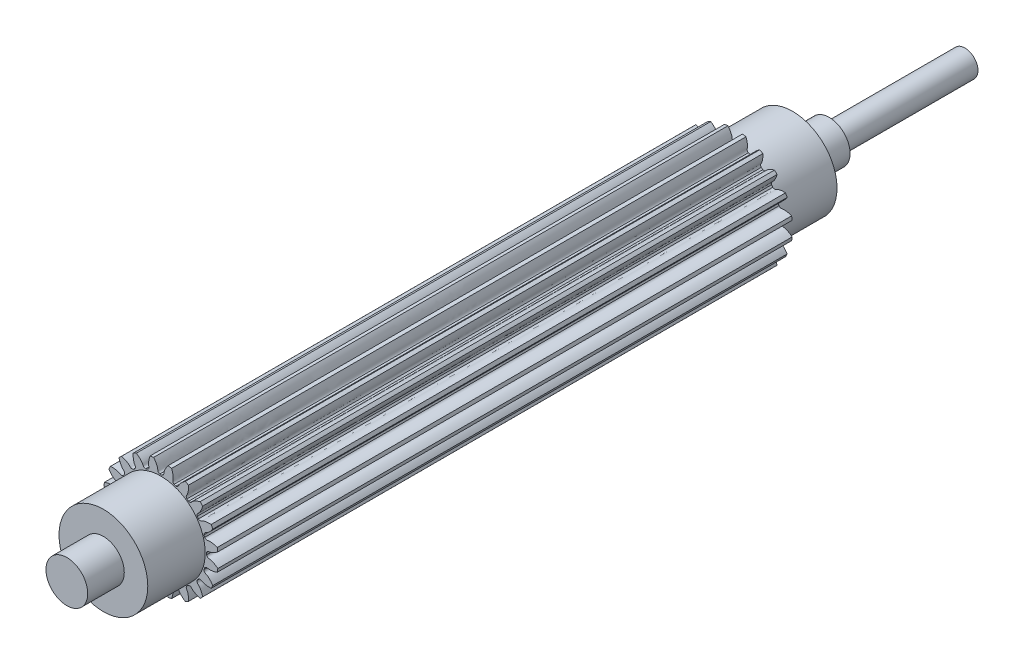
SolidWorks part; units mm, degrees
ref_plane "前视基准面" through (0, 0, 0) normal (0, 0, 1) x (1, 0, 0)
ref_plane "上视基准面" through (0, 0, 0) normal (0, 1, 0) x (1, 0, 0)
ref_plane "右视基准面" through (0, 0, 0) normal (1, 0, 0) x (0, 0, -1)
sketch "草图1" plane through (0, 0, 0) normal (0, 0, 1) x (1, 0, 0)
  circle A0 centre (0, 0) radius 11
extrude "凸台-拉伸1" add sketch "草图1" along normal blind 30
ref_axis "基准轴1" through (0, 0, -1.5) along (0, 0, 1)
sketch "草图2" plane through (0, 0, 0) normal (0, 0, 1) x (1, 0, 0)
  line L0 (0, 0) -> (0, 11) construction
  circle A0 centre (0, 0) radius 11 construction
  arc A1 (0.1933, 8.7479) -> (-0.1933, 8.7479) centre (0, 0) ccw
  arc A2 (3.1812, 12.4983) -> (-3.1812, 12.4983) centre (0, 0) ccw
  spline S0 degree 3 poles (0.1933, 8.7479) (0.6112, 8.8935) (0.5571, 9.1871) (0.6129, 9.47) (0.6189, 9.4976) (0.6263, 9.5286) (0.6353, 9.5632) (0.646, 9.6012) (0.6585, 9.6426) (0.673, 9.6873) (0.6897, 9.7352) (0.7086, 9.7863) (0.7299, 9.8406) (0.7537, 9.8978) (0.7801, 9.958) (0.8094, 10.0211) (0.8415, 10.087) (0.8767, 10.1556) (0.915, 10.2267) (0.9566, 10.3004) (1.0015, 10.3764) (1.05, 10.4548) (1.102, 10.5352) (1.1578, 10.6178) (1.2173, 10.7023) (1.2808, 10.7886) (1.3482, 10.8766) (1.4198, 10.9662) (1.4955, 11.0572) (1.5755, 11.1496) (1.6598, 11.2431) (1.7486, 11.3376) (1.8418, 11.4331) (1.9397, 11.5293) (2.0421, 11.6261) (2.1493, 11.7233) (2.2612, 11.8209) (2.378, 11.9186) (2.4996, 12.0163) (2.6261, 12.1139) (2.7575, 12.2112) (2.9415, 12.3416) (3.0839, 12.4363) (3.1812, 12.4983) knots 0 0 0 0 0.165916 0.170906 0.176664 0.183189 0.190482 0.198542 0.207371 0.216967 0.22733 0.238462 0.250361 0.263027 0.276462 0.290664 0.305634 0.321371 0.337876 0.355149 0.37319 0.391998 0.411574 0.431917 0.453028 0.474907 0.497554 0.520968 0.54515 0.570099 0.595817 0.622302 0.649554 0.677575 0.706363 0.735918 0.766242 0.797333 0.829191 0.861818 0.895212 0.929373 1 1 1 1
  spline S1 degree 3 poles (-0.1933, 8.7479) (-0.6112, 8.8935) (-0.5571, 9.1871) (-0.6129, 9.47) (-0.6189, 9.4976) (-0.6263, 9.5286) (-0.6353, 9.5632) (-0.646, 9.6012) (-0.6585, 9.6426) (-0.673, 9.6873) (-0.6897, 9.7352) (-0.7086, 9.7863) (-0.7299, 9.8406) (-0.7537, 9.8978) (-0.7801, 9.958) (-0.8094, 10.0211) (-0.8415, 10.087) (-0.8767, 10.1556) (-0.915, 10.2267) (-0.9566, 10.3004) (-1.0015, 10.3764) (-1.05, 10.4548) (-1.102, 10.5352) (-1.1578, 10.6178) (-1.2173, 10.7023) (-1.2808, 10.7886) (-1.3482, 10.8766) (-1.4198, 10.9662) (-1.4955, 11.0572) (-1.5755, 11.1496) (-1.6598, 11.2431) (-1.7486, 11.3376) (-1.8418, 11.4331) (-1.9397, 11.5293) (-2.0421, 11.6261) (-2.1493, 11.7233) (-2.2612, 11.8209) (-2.378, 11.9186) (-2.4996, 12.0163) (-2.6261, 12.1139) (-2.7575, 12.2112) (-2.9415, 12.3416) (-3.0839, 12.4363) (-3.1812, 12.4983) knots 0 0 0 0 0.165916 0.170906 0.176664 0.183189 0.190482 0.198542 0.207371 0.216967 0.22733 0.238462 0.250361 0.263027 0.276462 0.290664 0.305634 0.321371 0.337876 0.355149 0.37319 0.391998 0.411574 0.431917 0.453028 0.474907 0.497554 0.520968 0.54515 0.570099 0.595817 0.622302 0.649554 0.677575 0.706363 0.735918 0.766242 0.797333 0.829191 0.861818 0.895212 0.929373 1 1 1 1
extrude "切除-拉伸1" cut sketch "草图2" along normal through all
pattern_circular "阵列(圆周)1" count 20 every 18 about axis through (0, 0, -1.5) along (0, 0, 1) of "切除-拉伸1"
sketch "草图3" plane through (0, 0, 0) normal (0, 0, 1) x (1, 0, 0)
  circle A0 centre (0, 0) radius 10 construction
  dimension "Dn" = 20
sketch "草图4" plane through (0, 0, 30) normal (0, 0, 1) x (1, 0, 0)
  arc A41 (-2.5194, 8.3795) -> (-2.8871, 8.26) centre (0, 0) ccw
  arc A42 (-4.6827, 9.9535) -> (-5.3001, 9.6389) centre (0, 0) ccw
  arc A43 (-4.9855, 7.1908) -> (-5.2983, 6.9635) centre (0, 0) ccw
  arc A44 (-7.5293, 8.0193) -> (-8.0193, 7.5293) centre (0, 0) ccw
  arc A45 (-6.9635, 5.2983) -> (-7.1908, 4.9855) centre (0, 0) ccw
  arc A46 (-9.6389, 5.3001) -> (-9.9535, 4.6827) centre (0, 0) ccw
  arc A47 (-8.26, 2.8871) -> (-8.3795, 2.5194) centre (0, 0) ccw
  arc A48 (-10.805, 2.0622) -> (-10.9134, 1.3777) centre (0, 0) ccw
  arc A49 (-8.7479, 0.1933) -> (-8.7479, -0.1933) centre (0, 0) ccw
  arc A50 (-10.9134, -1.3777) -> (-10.805, -2.0622) centre (0, 0) ccw
  arc A51 (-8.3795, -2.5194) -> (-8.26, -2.8871) centre (0, 0) ccw
  arc A52 (-9.9535, -4.6827) -> (-9.6389, -5.3001) centre (0, 0) ccw
  arc A53 (-7.1908, -4.9855) -> (-6.9635, -5.2983) centre (0, 0) ccw
  arc A54 (-8.0193, -7.5293) -> (-7.5293, -8.0193) centre (0, 0) ccw
  arc A55 (-5.2983, -6.9635) -> (-4.9855, -7.1908) centre (0, 0) ccw
  arc A56 (-5.3001, -9.6389) -> (-4.6827, -9.9535) centre (0, 0) ccw
  arc A57 (-2.8871, -8.26) -> (-2.5194, -8.3795) centre (0, 0) ccw
  arc A58 (-2.0622, -10.805) -> (-1.3777, -10.9134) centre (0, 0) ccw
  arc A59 (-0.1933, -8.7479) -> (0.1933, -8.7479) centre (0, 0) ccw
  arc A60 (1.3777, -10.9134) -> (2.0622, -10.805) centre (0, 0) ccw
  arc A61 (2.5194, -8.3795) -> (2.8871, -8.26) centre (0, 0) ccw
  arc A62 (4.6827, -9.9535) -> (5.3001, -9.6389) centre (0, 0) ccw
  arc A63 (4.9855, -7.1908) -> (5.2983, -6.9635) centre (0, 0) ccw
  arc A64 (7.5293, -8.0193) -> (8.0193, -7.5293) centre (0, 0) ccw
  arc A65 (6.9635, -5.2983) -> (7.1908, -4.9855) centre (0, 0) ccw
  arc A66 (9.6389, -5.3001) -> (9.9535, -4.6827) centre (0, 0) ccw
  arc A67 (8.26, -2.8871) -> (8.3795, -2.5194) centre (0, 0) ccw
  arc A68 (10.805, -2.0622) -> (10.9134, -1.3777) centre (0, 0) ccw
  arc A69 (8.7479, -0.1933) -> (8.7479, 0.1933) centre (0, 0) ccw
  arc A70 (10.9134, 1.3777) -> (10.805, 2.0622) centre (0, 0) ccw
  arc A71 (8.3795, 2.5194) -> (8.26, 2.8871) centre (0, 0) ccw
  arc A72 (9.9535, 4.6827) -> (9.6389, 5.3001) centre (0, 0) ccw
  arc A73 (7.1908, 4.9855) -> (6.9635, 5.2983) centre (0, 0) ccw
  arc A74 (8.0193, 7.5293) -> (7.5293, 8.0193) centre (0, 0) ccw
  arc A75 (5.2983, 6.9635) -> (4.9855, 7.1908) centre (0, 0) ccw
  arc A76 (5.3001, 9.6389) -> (4.6827, 9.9535) centre (0, 0) ccw
  arc A77 (2.8871, 8.26) -> (2.5194, 8.3795) centre (0, 0) ccw
  arc A78 (2.0622, 10.805) -> (1.3777, 10.9134) centre (0, 0) ccw
  arc A79 (0.1933, 8.7479) -> (-0.1933, 8.7479) centre (0, 0) ccw
  arc A80 (-1.3777, 10.9134) -> (-2.0622, 10.805) centre (0, 0) ccw
  arc A81 (-2.5194, 8.3795) -> (-2.8871, 8.26) centre (0, 0) ccw
  arc A82 (-4.6827, 9.9535) -> (-5.3001, 9.6389) centre (0, 0) ccw
  arc A83 (-4.9855, 7.1908) -> (-5.2983, 6.9635) centre (0, 0) ccw
  arc A84 (-7.5293, 8.0193) -> (-8.0193, 7.5293) centre (0, 0) ccw
  arc A85 (-6.9635, 5.2983) -> (-7.1908, 4.9855) centre (0, 0) ccw
  arc A86 (-9.6389, 5.3001) -> (-9.9535, 4.6827) centre (0, 0) ccw
  arc A87 (-8.26, 2.8871) -> (-8.3795, 2.5194) centre (0, 0) ccw
  arc A88 (-10.805, 2.0622) -> (-10.9134, 1.3777) centre (0, 0) ccw
  arc A89 (-8.7479, 0.1933) -> (-8.7479, -0.1933) centre (0, 0) ccw
  arc A90 (-10.9134, -1.3777) -> (-10.805, -2.0622) centre (0, 0) ccw
  arc A91 (-8.3795, -2.5194) -> (-8.26, -2.8871) centre (0, 0) ccw
  arc A92 (-9.9535, -4.6827) -> (-9.6389, -5.3001) centre (0, 0) ccw
  arc A93 (-7.1908, -4.9855) -> (-6.9635, -5.2983) centre (0, 0) ccw
  arc A94 (-8.0193, -7.5293) -> (-7.5293, -8.0193) centre (0, 0) ccw
  arc A95 (-5.2983, -6.9635) -> (-4.9855, -7.1908) centre (0, 0) ccw
  arc A96 (-5.3001, -9.6389) -> (-4.6827, -9.9535) centre (0, 0) ccw
  arc A97 (-2.8871, -8.26) -> (-2.5194, -8.3795) centre (0, 0) ccw
  arc A98 (-2.0622, -10.805) -> (-1.3777, -10.9134) centre (0, 0) ccw
  arc A99 (-0.1933, -8.7479) -> (0.1933, -8.7479) centre (0, 0) ccw
  arc A100 (1.3777, -10.9134) -> (2.0622, -10.805) centre (0, 0) ccw
  arc A101 (2.5194, -8.3795) -> (2.8871, -8.26) centre (0, 0) ccw
  arc A102 (4.6827, -9.9535) -> (5.3001, -9.6389) centre (0, 0) ccw
  arc A103 (4.9855, -7.1908) -> (5.2983, -6.9635) centre (0, 0) ccw
  arc A104 (7.5293, -8.0193) -> (8.0193, -7.5293) centre (0, 0) ccw
  arc A105 (6.9635, -5.2983) -> (7.1908, -4.9855) centre (0, 0) ccw
  arc A106 (9.6389, -5.3001) -> (9.9535, -4.6827) centre (0, 0) ccw
  arc A107 (8.26, -2.8871) -> (8.3795, -2.5194) centre (0, 0) ccw
  arc A108 (10.805, -2.0622) -> (10.9134, -1.3777) centre (0, 0) ccw
  arc A109 (8.7479, -0.1933) -> (8.7479, 0.1933) centre (0, 0) ccw
  arc A110 (10.9134, 1.3777) -> (10.805, 2.0622) centre (0, 0) ccw
  arc A111 (8.3795, 2.5194) -> (8.26, 2.8871) centre (0, 0) ccw
  arc A112 (9.9535, 4.6827) -> (9.6389, 5.3001) centre (0, 0) ccw
  arc A113 (7.1908, 4.9855) -> (6.9635, 5.2983) centre (0, 0) ccw
  arc A114 (8.0193, 7.5293) -> (7.5293, 8.0193) centre (0, 0) ccw
  arc A115 (5.2983, 6.9635) -> (4.9855, 7.1908) centre (0, 0) ccw
  arc A116 (5.3001, 9.6389) -> (4.6827, 9.9535) centre (0, 0) ccw
  arc A117 (2.8871, 8.26) -> (2.5194, 8.3795) centre (0, 0) ccw
  arc A118 (2.0622, 10.805) -> (1.3777, 10.9134) centre (0, 0) ccw
  arc A119 (0.1933, 8.7479) -> (-0.1933, 8.7479) centre (0, 0) ccw
  arc A120 (-1.3777, 10.9134) -> (-2.0622, 10.805) centre (0, 0) ccw
  spline S40 degree 3 poles (3336.3224, 2209.2476) (-31.6692, -18.2216) (-0.9853, 4.2936) (-3.5145, 8.8264) (-3.5419, 8.8721) (-3.5831, 8.935) (-3.6355, 9.0085) (-3.6999, 9.0917) (-3.7774, 9.1837) (-3.8685, 9.2838) (-3.9742, 9.3908) (-4.095, 9.5038) (-4.2316, 9.6217) (-4.3846, 9.7434) (-24.8231, 24.7147) (-146.1058, -103.9868) (3698.5838, 1520.9008) knots -2.504414 -2.504414 -2.504414 -2.504414 0.658484 0.663474 0.675757 0.691111 0.709535 0.73103 0.755596 0.783232 0.813939 0.847717 0.884566 0.924485 0.967475 16.40464 16.40464 16.40464 16.40464 only from (-2.8871, 8.26) to (-4.6827, 9.9535)
  spline S41 degree 3 poles (-3401.5075, -2102.9172) (167.7752, 59.3862) (-5.894, 33.9751) (-5.3021, 9.1747) (-5.2901, 8.9871) (-5.2722, 8.8151) (-5.2496, 8.6588) (-5.2235, 8.5183) (-5.1952, 8.3937) (-5.1658, 8.2848) (-5.1406, 8.204) (-5.1169, 8.136) (-5.0958, 8.0803) (-5.075, 8.0313) (-2.8945, 3.3208) (33.3564, 14.9106) (-3748.3817, -1400.5865) knots -15.062528 -15.062528 -15.062528 -15.062528 0.054403 0.095858 0.134242 0.169555 0.201798 0.23097 0.257071 0.280101 0.300061 0.308889 0.324243 0.336526 0.341516 3.50442 3.50442 3.50442 3.50442 only from (-5.3001, 9.6389) to (-4.9855, 7.1908)
  spline S42 degree 3 poles (2490.3361, 3132.0996) (-24.4884, -27.1161) (-2.2639, 3.779) (-6.07, 7.3084) (-6.1102, 7.3434) (-6.1688, 7.3905) (-6.2413, 7.4441) (-6.3283, 7.5033) (-6.4304, 7.567) (-6.548, 7.634) (-6.6816, 7.7031) (-6.8314, 7.7732) (-6.9977, 7.8432) (-7.1808, 7.9117) (-31.2455, 15.8343) (-106.8212, -144.0465) (3047.578, 2589.3879) knots -2.504414 -2.504414 -2.504414 -2.504414 0.658484 0.663474 0.675757 0.691111 0.709535 0.73103 0.755596 0.783232 0.813939 0.847717 0.884566 0.924485 0.967475 16.40464 16.40464 16.40464 16.40464 only from (-5.2983, 6.9635) to (-7.5293, 8.0193)
  spline S43 degree 3 poles (-2585.1887, -3051.1167) (141.2124, 108.325) (-16.1044, 30.4909) (-7.8777, 7.0872) (-7.8083, 6.9125) (-7.7381, 6.7544) (-7.6683, 6.6128) (-7.6001, 6.4873) (-7.5347, 6.3775) (-7.4731, 6.283) (-7.4241, 6.214) (-7.3806, 6.1566) (-7.3434, 6.1102) (-7.3084, 6.07) (-3.779, 2.2639) (27.1162, 24.4885) (-3132.1178, -2490.3506) knots -15.062528 -15.062528 -15.062528 -15.062528 0.054403 0.095858 0.134242 0.169555 0.201798 0.23097 0.257071 0.280101 0.300061 0.308889 0.324243 0.336526 0.341516 3.50442 3.50442 3.50442 3.50442 only from (-8.0193, 7.5293) to (-6.9635, 5.2983)
  spline S44 degree 3 poles (1400.5784, 3748.36) (-14.9105, -33.3563) (-3.3209, 2.8945) (-8.0313, 5.075) (-8.0803, 5.0958) (-8.1506, 5.1225) (-8.2362, 5.1511) (-8.3373, 5.1805) (-8.454, 5.2095) (-8.5866, 5.2369) (-8.7349, 5.2614) (-8.8991, 5.2818) (-9.0789, 5.2969) (-9.2742, 5.3054) (-34.6093, 5.404) (-57.0802, -170.0059) (2098.2541, 3404.4076) knots -2.504414 -2.504414 -2.504414 -2.504414 0.658484 0.663474 0.675757 0.691111 0.709535 0.73103 0.755596 0.783232 0.813939 0.847717 0.884566 0.924485 0.967475 16.40464 16.40464 16.40464 16.40464 only from (-7.1908, 4.9855) to (-9.6389, 5.3001)
  spline S45 degree 3 poles (-1515.8137, -3700.6517) (100.8267, 146.6603) (-24.7384, 24.022) (-9.6822, 4.306) (-9.5622, 4.1613) (-9.4466, 4.0326) (-9.3365, 3.9195) (-9.2328, 3.8212) (-9.1366, 3.737) (-9.0489, 3.6661) (-8.981, 3.6157) (-8.9219, 3.5745) (-8.8721, 3.5419) (-8.8264, 3.5145) (-4.2936, 0.9853) (18.2217, 31.6693) (-2209.2604, -3336.3418) knots -15.062528 -15.062528 -15.062528 -15.062528 0.054403 0.095858 0.134242 0.169555 0.201798 0.23097 0.257071 0.280101 0.300061 0.308889 0.324243 0.336526 0.341516 3.50442 3.50442 3.50442 3.50442 only from (-9.9535, 4.6827) to (-8.26, 2.8871)
  spline S46 degree 3 poles (173.7222, 3997.7047) (-3.8731, -36.3313) (-4.0528, 1.7266) (-9.2065, 2.3448) (-9.2595, 2.3494) (-9.3346, 2.3531) (-9.4249, 2.3539) (-9.5301, 2.3506) (-9.6501, 2.3421) (-9.7846, 2.3272) (-9.9333, 2.3046) (-10.0957, 2.2733) (-10.2714, 2.2321) (-10.4598, 2.1799) (-34.5853, -5.5554) (-1.7518, -179.324) (943.5384, 3886.1802) knots -2.504414 -2.504414 -2.504414 -2.504414 0.658484 0.663474 0.675757 0.691111 0.709535 0.73103 0.755596 0.783232 0.813939 0.847717 0.884566 0.924485 0.967475 16.40464 16.40464 16.40464 16.40464 only from (-8.3795, 2.5194) to (-10.805, 2.0622)
  spline S47 degree 3 poles (-298.0602, -3987.9411) (50.5714, 170.6393) (-30.9508, 15.2017) (-10.5389, 1.1033) (-10.3801, 1.0027) (-10.2304, 0.9161) (-10.0907, 0.8425) (-9.9617, 0.7811) (-9.8443, 0.7307) (-9.7389, 0.6904) (-9.6588, 0.6634) (-9.5898, 0.6425) (-9.5324, 0.6269) (-9.4805, 0.615) (-4.388, -0.3897) (7.5435, 35.7501) (-1070.1452, -3855.7486) knots -15.062528 -15.062528 -15.062528 -15.062528 0.054403 0.095858 0.134242 0.169555 0.201798 0.23097 0.257071 0.280101 0.300061 0.308889 0.324243 0.336526 0.341516 3.50442 3.50442 3.50442 3.50442 only from (-10.9134, 1.3777) to (-8.7479, 0.1933)
  spline S48 degree 3 poles (-1070.139, 3855.7262) (7.5434, -35.75) (-4.388, 0.3897) (-9.4805, -0.615) (-9.5324, -0.6269) (-9.6049, -0.6466) (-9.691, -0.6738) (-9.79, -0.7094) (-9.9015, -0.7546) (-10.0248, -0.8103) (-10.1593, -0.8777) (-10.3041, -0.9577) (-10.4584, -1.0512) (-10.6215, -1.1591) (-31.1759, -15.9709) (53.7481, -171.0886) (-303.5374, 3987.5464) knots -2.504414 -2.504414 -2.504414 -2.504414 0.658484 0.663474 0.675757 0.691111 0.709535 0.73103 0.755596 0.783232 0.813939 0.847717 0.884566 0.924485 0.967475 16.40464 16.40464 16.40464 16.40464 only from (-8.7479, -0.1933) to (-10.9134, -1.3777)
  spline S49 degree 3 poles (948.8694, -3884.863) (-4.6342, 177.9151) (-34.1335, 4.8934) (-10.364, -2.2074) (-10.1819, -2.254) (-10.0128, -2.2901) (-9.8572, -2.3169) (-9.7155, -2.3355) (-9.5882, -2.3471) (-9.4756, -2.3528) (-9.391, -2.3538) (-9.319, -2.3523) (-9.2595, -2.3494) (-9.2065, -2.3448) (-4.0528, -1.7266) (-3.8731, 36.3314) (173.7233, -3997.7279) knots -15.062528 -15.062528 -15.062528 -15.062528 0.054403 0.095858 0.134242 0.169555 0.201798 0.23097 0.257071 0.280101 0.300061 0.308889 0.324243 0.336526 0.341516 3.50442 3.50442 3.50442 3.50442 only from (-10.805, -2.0622) to (-8.3795, -2.5194)
  spline S50 degree 3 poles (-2209.2476, 3336.3224) (18.2216, -31.6692) (-4.2936, -0.9853) (-8.8264, -3.5145) (-8.8721, -3.5419) (-8.935, -3.5831) (-9.0085, -3.6355) (-9.0917, -3.6999) (-9.1837, -3.7774) (-9.2838, -3.8685) (-9.3908, -3.9742) (-9.5038, -4.095) (-9.6217, -4.2316) (-9.7434, -4.3846) (-24.7147, -24.8231) (103.9868, -146.1058) (-1520.9008, 3698.5838) knots -2.504414 -2.504414 -2.504414 -2.504414 0.658484 0.663474 0.675757 0.691111 0.709535 0.73103 0.755596 0.783232 0.813939 0.847717 0.884566 0.924485 0.967475 16.40464 16.40464 16.40464 16.40464 only from (-8.26, -2.8871) to (-9.9535, -4.6827)
  spline S51 degree 3 poles (2102.9172, -3401.5075) (-59.3862, 167.7752) (-33.9751, -5.894) (-9.1747, -5.3021) (-8.9871, -5.2901) (-8.8151, -5.2722) (-8.6588, -5.2496) (-8.5183, -5.2235) (-8.3937, -5.1952) (-8.2848, -5.1658) (-8.204, -5.1406) (-8.136, -5.1169) (-8.0803, -5.0958) (-8.0313, -5.075) (-3.3208, -2.8945) (-14.9106, 33.3564) (1400.5865, -3748.3817) knots -15.062528 -15.062528 -15.062528 -15.062528 0.054403 0.095858 0.134242 0.169555 0.201798 0.23097 0.257071 0.280101 0.300061 0.308889 0.324243 0.336526 0.341516 3.50442 3.50442 3.50442 3.50442 only from (-9.6389, -5.3001) to (-7.1908, -4.9855)
  spline S52 degree 3 poles (-3132.0996, 2490.3361) (27.1161, -24.4884) (-3.779, -2.2639) (-7.3084, -6.07) (-7.3434, -6.1102) (-7.3905, -6.1688) (-7.4441, -6.2413) (-7.5033, -6.3283) (-7.567, -6.4304) (-7.634, -6.548) (-7.7031, -6.6816) (-7.7732, -6.8314) (-7.8432, -6.9977) (-7.9117, -7.1808) (-15.8343, -31.2455) (144.0465, -106.8212) (-2589.3879, 3047.578) knots -2.504414 -2.504414 -2.504414 -2.504414 0.658484 0.663474 0.675757 0.691111 0.709535 0.73103 0.755596 0.783232 0.813939 0.847717 0.884566 0.924485 0.967475 16.40464 16.40464 16.40464 16.40464 only from (-6.9635, -5.2983) to (-8.0193, -7.5293)
  spline S53 degree 3 poles (3051.1167, -2585.1887) (-108.325, 141.2124) (-30.4909, -16.1044) (-7.0872, -7.8777) (-6.9125, -7.8083) (-6.7544, -7.7381) (-6.6128, -7.6683) (-6.4873, -7.6001) (-6.3775, -7.5347) (-6.283, -7.4731) (-6.214, -7.4241) (-6.1566, -7.3806) (-6.1102, -7.3434) (-6.07, -7.3084) (-2.2639, -3.779) (-24.4885, 27.1162) (2490.3506, -3132.1178) knots -15.062528 -15.062528 -15.062528 -15.062528 0.054403 0.095858 0.134242 0.169555 0.201798 0.23097 0.257071 0.280101 0.300061 0.308889 0.324243 0.336526 0.341516 3.50442 3.50442 3.50442 3.50442 only from (-7.5293, -8.0193) to (-5.2983, -6.9635)
  spline S54 degree 3 poles (-3748.36, 1400.5784) (33.3563, -14.9105) (-2.8945, -3.3209) (-5.075, -8.0313) (-5.0958, -8.0803) (-5.1225, -8.1506) (-5.1511, -8.2362) (-5.1805, -8.3373) (-5.2095, -8.454) (-5.2369, -8.5866) (-5.2614, -8.7349) (-5.2818, -8.8991) (-5.2969, -9.0789) (-5.3054, -9.2742) (-5.404, -34.6093) (170.0059, -57.0802) (-3404.4076, 2098.2541) knots -2.504414 -2.504414 -2.504414 -2.504414 0.658484 0.663474 0.675757 0.691111 0.709535 0.73103 0.755596 0.783232 0.813939 0.847717 0.884566 0.924485 0.967475 16.40464 16.40464 16.40464 16.40464 only from (-4.9855, -7.1908) to (-5.3001, -9.6389)
  spline S55 degree 3 poles (3700.6517, -1515.8137) (-146.6603, 100.8267) (-24.022, -24.7384) (-4.306, -9.6822) (-4.1613, -9.5622) (-4.0326, -9.4466) (-3.9195, -9.3365) (-3.8212, -9.2328) (-3.737, -9.1366) (-3.6661, -9.0489) (-3.6157, -8.981) (-3.5745, -8.9219) (-3.5419, -8.8721) (-3.5145, -8.8264) (-0.9853, -4.2936) (-31.6693, 18.2217) (3336.3418, -2209.2604) knots -15.062528 -15.062528 -15.062528 -15.062528 0.054403 0.095858 0.134242 0.169555 0.201798 0.23097 0.257071 0.280101 0.300061 0.308889 0.324243 0.336526 0.341516 3.50442 3.50442 3.50442 3.50442 only from (-4.6827, -9.9535) to (-2.8871, -8.26)
  spline S56 degree 3 poles (-3997.7047, 173.7222) (36.3313, -3.8731) (-1.7266, -4.0528) (-2.3448, -9.2065) (-2.3494, -9.2595) (-2.3531, -9.3346) (-2.3539, -9.4249) (-2.3506, -9.5301) (-2.3421, -9.6501) (-2.3272, -9.7846) (-2.3046, -9.9333) (-2.2733, -10.0957) (-2.2321, -10.2714) (-2.1799, -10.4598) (5.5554, -34.5853) (179.324, -1.7518) (-3886.1802, 943.5384) knots -2.504414 -2.504414 -2.504414 -2.504414 0.658484 0.663474 0.675757 0.691111 0.709535 0.73103 0.755596 0.783232 0.813939 0.847717 0.884566 0.924485 0.967475 16.40464 16.40464 16.40464 16.40464 only from (-2.5194, -8.3795) to (-2.0622, -10.805)
  spline S57 degree 3 poles (3987.9411, -298.0602) (-170.6393, 50.5714) (-15.2017, -30.9508) (-1.1033, -10.5389) (-1.0027, -10.3801) (-0.9161, -10.2304) (-0.8425, -10.0907) (-0.7811, -9.9617) (-0.7307, -9.8443) (-0.6904, -9.7389) (-0.6634, -9.6588) (-0.6425, -9.5898) (-0.6269, -9.5324) (-0.615, -9.4805) (0.3897, -4.388) (-35.7501, 7.5435) (3855.7486, -1070.1452) knots -15.062528 -15.062528 -15.062528 -15.062528 0.054403 0.095858 0.134242 0.169555 0.201798 0.23097 0.257071 0.280101 0.300061 0.308889 0.324243 0.336526 0.341516 3.50442 3.50442 3.50442 3.50442 only from (-1.3777, -10.9134) to (-0.1933, -8.7479)
  spline S58 degree 3 poles (-3855.7262, -1070.139) (35.75, 7.5434) (-0.3897, -4.388) (0.615, -9.4805) (0.6269, -9.5324) (0.6466, -9.6049) (0.6738, -9.691) (0.7094, -9.79) (0.7546, -9.9015) (0.8103, -10.0248) (0.8777, -10.1593) (0.9577, -10.3041) (1.0512, -10.4584) (1.1591, -10.6215) (15.9709, -31.1759) (171.0886, 53.7481) (-3987.5464, -303.5374) knots -2.504414 -2.504414 -2.504414 -2.504414 0.658484 0.663474 0.675757 0.691111 0.709535 0.73103 0.755596 0.783232 0.813939 0.847717 0.884566 0.924485 0.967475 16.40464 16.40464 16.40464 16.40464 only from (0.1933, -8.7479) to (1.3777, -10.9134)
  spline S59 degree 3 poles (3884.863, 948.8694) (-177.9151, -4.6342) (-4.8934, -34.1335) (2.2074, -10.364) (2.254, -10.1819) (2.2901, -10.0128) (2.3169, -9.8572) (2.3355, -9.7155) (2.3471, -9.5882) (2.3528, -9.4756) (2.3538, -9.391) (2.3523, -9.319) (2.3494, -9.2595) (2.3448, -9.2065) (1.7266, -4.0528) (-36.3314, -3.8731) (3997.7279, 173.7233) knots -15.062528 -15.062528 -15.062528 -15.062528 0.054403 0.095858 0.134242 0.169555 0.201798 0.23097 0.257071 0.280101 0.300061 0.308889 0.324243 0.336526 0.341516 3.50442 3.50442 3.50442 3.50442 only from (2.0622, -10.805) to (2.5194, -8.3795)
  spline S60 degree 3 poles (-3336.3224, -2209.2476) (31.6692, 18.2216) (0.9853, -4.2936) (3.5145, -8.8264) (3.5419, -8.8721) (3.5831, -8.935) (3.6355, -9.0085) (3.6999, -9.0917) (3.7774, -9.1837) (3.8685, -9.2838) (3.9742, -9.3908) (4.095, -9.5038) (4.2316, -9.6217) (4.3846, -9.7434) (24.8231, -24.7147) (146.1058, 103.9868) (-3698.5838, -1520.9008) knots -2.504414 -2.504414 -2.504414 -2.504414 0.658484 0.663474 0.675757 0.691111 0.709535 0.73103 0.755596 0.783232 0.813939 0.847717 0.884566 0.924485 0.967475 16.40464 16.40464 16.40464 16.40464 only from (2.8871, -8.26) to (4.6827, -9.9535)
  spline S61 degree 3 poles (3401.5075, 2102.9172) (-167.7752, -59.3862) (5.894, -33.9751) (5.3021, -9.1747) (5.2901, -8.9871) (5.2722, -8.8151) (5.2496, -8.6588) (5.2235, -8.5183) (5.1952, -8.3937) (5.1658, -8.2848) (5.1406, -8.204) (5.1169, -8.136) (5.0958, -8.0803) (5.075, -8.0313) (2.8945, -3.3208) (-33.3564, -14.9106) (3748.3817, 1400.5865) knots -15.062528 -15.062528 -15.062528 -15.062528 0.054403 0.095858 0.134242 0.169555 0.201798 0.23097 0.257071 0.280101 0.300061 0.308889 0.324243 0.336526 0.341516 3.50442 3.50442 3.50442 3.50442 only from (5.3001, -9.6389) to (4.9855, -7.1908)
  spline S62 degree 3 poles (-2490.3361, -3132.0996) (24.4884, 27.1161) (2.2639, -3.779) (6.07, -7.3084) (6.1102, -7.3434) (6.1688, -7.3905) (6.2413, -7.4441) (6.3283, -7.5033) (6.4304, -7.567) (6.548, -7.634) (6.6816, -7.7031) (6.8314, -7.7732) (6.9977, -7.8432) (7.1808, -7.9117) (31.2455, -15.8343) (106.8212, 144.0465) (-3047.578, -2589.3879) knots -2.504414 -2.504414 -2.504414 -2.504414 0.658484 0.663474 0.675757 0.691111 0.709535 0.73103 0.755596 0.783232 0.813939 0.847717 0.884566 0.924485 0.967475 16.40464 16.40464 16.40464 16.40464 only from (5.2983, -6.9635) to (7.5293, -8.0193)
  spline S63 degree 3 poles (2585.1887, 3051.1167) (-141.2124, -108.325) (16.1044, -30.4909) (7.8777, -7.0872) (7.8083, -6.9125) (7.7381, -6.7544) (7.6683, -6.6128) (7.6001, -6.4873) (7.5347, -6.3775) (7.4731, -6.283) (7.4241, -6.214) (7.3806, -6.1566) (7.3434, -6.1102) (7.3084, -6.07) (3.779, -2.2639) (-27.1162, -24.4885) (3132.1178, 2490.3506) knots -15.062528 -15.062528 -15.062528 -15.062528 0.054403 0.095858 0.134242 0.169555 0.201798 0.23097 0.257071 0.280101 0.300061 0.308889 0.324243 0.336526 0.341516 3.50442 3.50442 3.50442 3.50442 only from (8.0193, -7.5293) to (6.9635, -5.2983)
  spline S64 degree 3 poles (-1400.5784, -3748.36) (14.9105, 33.3563) (3.3209, -2.8945) (8.0313, -5.075) (8.0803, -5.0958) (8.1506, -5.1225) (8.2362, -5.1511) (8.3373, -5.1805) (8.454, -5.2095) (8.5866, -5.2369) (8.7349, -5.2614) (8.8991, -5.2818) (9.0789, -5.2969) (9.2742, -5.3054) (34.6093, -5.404) (57.0802, 170.0059) (-2098.2541, -3404.4076) knots -2.504414 -2.504414 -2.504414 -2.504414 0.658484 0.663474 0.675757 0.691111 0.709535 0.73103 0.755596 0.783232 0.813939 0.847717 0.884566 0.924485 0.967475 16.40464 16.40464 16.40464 16.40464 only from (7.1908, -4.9855) to (9.6389, -5.3001)
  spline S65 degree 3 poles (1515.8137, 3700.6517) (-100.8267, -146.6603) (24.7384, -24.022) (9.6822, -4.306) (9.5622, -4.1613) (9.4466, -4.0326) (9.3365, -3.9195) (9.2328, -3.8212) (9.1366, -3.737) (9.0489, -3.6661) (8.981, -3.6157) (8.9219, -3.5745) (8.8721, -3.5419) (8.8264, -3.5145) (4.2936, -0.9853) (-18.2217, -31.6693) (2209.2604, 3336.3418) knots -15.062528 -15.062528 -15.062528 -15.062528 0.054403 0.095858 0.134242 0.169555 0.201798 0.23097 0.257071 0.280101 0.300061 0.308889 0.324243 0.336526 0.341516 3.50442 3.50442 3.50442 3.50442 only from (9.9535, -4.6827) to (8.26, -2.8871)
  spline S66 degree 3 poles (-173.7222, -3997.7047) (3.8731, 36.3313) (4.0528, -1.7266) (9.2065, -2.3448) (9.2595, -2.3494) (9.3346, -2.3531) (9.4249, -2.3539) (9.5301, -2.3506) (9.6501, -2.3421) (9.7846, -2.3272) (9.9333, -2.3046) (10.0957, -2.2733) (10.2714, -2.2321) (10.4598, -2.1799) (34.5853, 5.5554) (1.7518, 179.324) (-943.5384, -3886.1802) knots -2.504414 -2.504414 -2.504414 -2.504414 0.658484 0.663474 0.675757 0.691111 0.709535 0.73103 0.755596 0.783232 0.813939 0.847717 0.884566 0.924485 0.967475 16.40464 16.40464 16.40464 16.40464 only from (8.3795, -2.5194) to (10.805, -2.0622)
  spline S67 degree 3 poles (298.0602, 3987.9411) (-50.5714, -170.6393) (30.9508, -15.2017) (10.5389, -1.1033) (10.3801, -1.0027) (10.2304, -0.9161) (10.0907, -0.8425) (9.9617, -0.7811) (9.8443, -0.7307) (9.7389, -0.6904) (9.6588, -0.6634) (9.5898, -0.6425) (9.5324, -0.6269) (9.4805, -0.615) (4.388, 0.3897) (-7.5435, -35.7501) (1070.1452, 3855.7486) knots -15.062528 -15.062528 -15.062528 -15.062528 0.054403 0.095858 0.134242 0.169555 0.201798 0.23097 0.257071 0.280101 0.300061 0.308889 0.324243 0.336526 0.341516 3.50442 3.50442 3.50442 3.50442 only from (10.9134, -1.3777) to (8.7479, -0.1933)
  spline S68 degree 3 poles (1070.139, -3855.7262) (-7.5434, 35.75) (4.388, -0.3897) (9.4805, 0.615) (9.5324, 0.6269) (9.6049, 0.6466) (9.691, 0.6738) (9.79, 0.7094) (9.9015, 0.7546) (10.0248, 0.8103) (10.1593, 0.8777) (10.3041, 0.9577) (10.4584, 1.0512) (10.6215, 1.1591) (31.1759, 15.9709) (-53.7481, 171.0886) (303.5374, -3987.5464) knots -2.504414 -2.504414 -2.504414 -2.504414 0.658484 0.663474 0.675757 0.691111 0.709535 0.73103 0.755596 0.783232 0.813939 0.847717 0.884566 0.924485 0.967475 16.40464 16.40464 16.40464 16.40464 only from (8.7479, 0.1933) to (10.9134, 1.3777)
  spline S69 degree 3 poles (-948.8694, 3884.863) (4.6342, -177.9151) (34.1335, -4.8934) (10.364, 2.2074) (10.1819, 2.254) (10.0128, 2.2901) (9.8572, 2.3169) (9.7155, 2.3355) (9.5882, 2.3471) (9.4756, 2.3528) (9.391, 2.3538) (9.319, 2.3523) (9.2595, 2.3494) (9.2065, 2.3448) (4.0528, 1.7266) (3.8731, -36.3314) (-173.7233, 3997.7279) knots -15.062528 -15.062528 -15.062528 -15.062528 0.054403 0.095858 0.134242 0.169555 0.201798 0.23097 0.257071 0.280101 0.300061 0.308889 0.324243 0.336526 0.341516 3.50442 3.50442 3.50442 3.50442 only from (10.805, 2.0622) to (8.3795, 2.5194)
  spline S70 degree 3 poles (2209.2476, -3336.3224) (-18.2216, 31.6692) (4.2936, 0.9853) (8.8264, 3.5145) (8.8721, 3.5419) (8.935, 3.5831) (9.0085, 3.6355) (9.0917, 3.6999) (9.1837, 3.7774) (9.2838, 3.8685) (9.3908, 3.9742) (9.5038, 4.095) (9.6217, 4.2316) (9.7434, 4.3846) (24.7147, 24.8231) (-103.9868, 146.1058) (1520.9008, -3698.5838) knots -2.504414 -2.504414 -2.504414 -2.504414 0.658484 0.663474 0.675757 0.691111 0.709535 0.73103 0.755596 0.783232 0.813939 0.847717 0.884566 0.924485 0.967475 16.40464 16.40464 16.40464 16.40464 only from (8.26, 2.8871) to (9.9535, 4.6827)
  spline S71 degree 3 poles (-2102.9172, 3401.5075) (59.3862, -167.7752) (33.9751, 5.894) (9.1747, 5.3021) (8.9871, 5.2901) (8.8151, 5.2722) (8.6588, 5.2496) (8.5183, 5.2235) (8.3937, 5.1952) (8.2848, 5.1658) (8.204, 5.1406) (8.136, 5.1169) (8.0803, 5.0958) (8.0313, 5.075) (3.3208, 2.8945) (14.9106, -33.3564) (-1400.5865, 3748.3817) knots -15.062528 -15.062528 -15.062528 -15.062528 0.054403 0.095858 0.134242 0.169555 0.201798 0.23097 0.257071 0.280101 0.300061 0.308889 0.324243 0.336526 0.341516 3.50442 3.50442 3.50442 3.50442 only from (9.6389, 5.3001) to (7.1908, 4.9855)
  spline S72 degree 3 poles (3132.0996, -2490.3361) (-27.1161, 24.4884) (3.779, 2.2639) (7.3084, 6.07) (7.3434, 6.1102) (7.3905, 6.1688) (7.4441, 6.2413) (7.5033, 6.3283) (7.567, 6.4304) (7.634, 6.548) (7.7031, 6.6816) (7.7732, 6.8314) (7.8432, 6.9977) (7.9117, 7.1808) (15.8343, 31.2455) (-144.0465, 106.8212) (2589.3879, -3047.578) knots -2.504414 -2.504414 -2.504414 -2.504414 0.658484 0.663474 0.675757 0.691111 0.709535 0.73103 0.755596 0.783232 0.813939 0.847717 0.884566 0.924485 0.967475 16.40464 16.40464 16.40464 16.40464 only from (6.9635, 5.2983) to (8.0193, 7.5293)
  spline S73 degree 3 poles (-3051.1167, 2585.1887) (108.325, -141.2124) (30.4909, 16.1044) (7.0872, 7.8777) (6.9125, 7.8083) (6.7544, 7.7381) (6.6128, 7.6683) (6.4873, 7.6001) (6.3775, 7.5347) (6.283, 7.4731) (6.214, 7.4241) (6.1566, 7.3806) (6.1102, 7.3434) (6.07, 7.3084) (2.2639, 3.779) (24.4885, -27.1162) (-2490.3506, 3132.1178) knots -15.062528 -15.062528 -15.062528 -15.062528 0.054403 0.095858 0.134242 0.169555 0.201798 0.23097 0.257071 0.280101 0.300061 0.308889 0.324243 0.336526 0.341516 3.50442 3.50442 3.50442 3.50442 only from (7.5293, 8.0193) to (5.2983, 6.9635)
  spline S74 degree 3 poles (3748.36, -1400.5784) (-33.3563, 14.9105) (2.8945, 3.3209) (5.075, 8.0313) (5.0958, 8.0803) (5.1225, 8.1506) (5.1511, 8.2362) (5.1805, 8.3373) (5.2095, 8.454) (5.2369, 8.5866) (5.2614, 8.7349) (5.2818, 8.8991) (5.2969, 9.0789) (5.3054, 9.2742) (5.404, 34.6093) (-170.0059, 57.0802) (3404.4076, -2098.2541) knots -2.504414 -2.504414 -2.504414 -2.504414 0.658484 0.663474 0.675757 0.691111 0.709535 0.73103 0.755596 0.783232 0.813939 0.847717 0.884566 0.924485 0.967475 16.40464 16.40464 16.40464 16.40464 only from (4.9855, 7.1908) to (5.3001, 9.6389)
  spline S75 degree 3 poles (-3700.6517, 1515.8137) (146.6603, -100.8267) (24.022, 24.7384) (4.306, 9.6822) (4.1613, 9.5622) (4.0326, 9.4466) (3.9195, 9.3365) (3.8212, 9.2328) (3.737, 9.1366) (3.6661, 9.0489) (3.6157, 8.981) (3.5745, 8.9219) (3.5419, 8.8721) (3.5145, 8.8264) (0.9853, 4.2936) (31.6693, -18.2217) (-3336.3418, 2209.2604) knots -15.062528 -15.062528 -15.062528 -15.062528 0.054403 0.095858 0.134242 0.169555 0.201798 0.23097 0.257071 0.280101 0.300061 0.308889 0.324243 0.336526 0.341516 3.50442 3.50442 3.50442 3.50442 only from (4.6827, 9.9535) to (2.8871, 8.26)
  spline S76 degree 3 poles (3997.7047, -173.7222) (-36.3313, 3.8731) (1.7266, 4.0528) (2.3448, 9.2065) (2.3494, 9.2595) (2.3531, 9.3346) (2.3539, 9.4249) (2.3506, 9.5301) (2.3421, 9.6501) (2.3272, 9.7846) (2.3046, 9.9333) (2.2733, 10.0957) (2.2321, 10.2714) (2.1799, 10.4598) (-5.5554, 34.5853) (-179.324, 1.7518) (3886.1802, -943.5384) knots -2.504414 -2.504414 -2.504414 -2.504414 0.658484 0.663474 0.675757 0.691111 0.709535 0.73103 0.755596 0.783232 0.813939 0.847717 0.884566 0.924485 0.967475 16.40464 16.40464 16.40464 16.40464 only from (2.5194, 8.3795) to (2.0622, 10.805)
  spline S77 degree 3 poles (-3987.9411, 298.0602) (170.6393, -50.5714) (15.2017, 30.9508) (1.1033, 10.5389) (1.0027, 10.3801) (0.9161, 10.2304) (0.8425, 10.0907) (0.7811, 9.9617) (0.7307, 9.8443) (0.6904, 9.7389) (0.6634, 9.6588) (0.6425, 9.5898) (0.6269, 9.5324) (0.615, 9.4805) (-0.3897, 4.388) (35.7501, -7.5435) (-3855.7486, 1070.1452) knots -15.062528 -15.062528 -15.062528 -15.062528 0.054403 0.095858 0.134242 0.169555 0.201798 0.23097 0.257071 0.280101 0.300061 0.308889 0.324243 0.336526 0.341516 3.50442 3.50442 3.50442 3.50442 only from (1.3777, 10.9134) to (0.1933, 8.7479)
  spline S78 degree 3 poles (3855.7262, 1070.139) (-35.75, -7.5434) (0.3897, 4.388) (-0.615, 9.4805) (-0.6269, 9.5324) (-0.6466, 9.6049) (-0.6738, 9.691) (-0.7094, 9.79) (-0.7546, 9.9015) (-0.8103, 10.0248) (-0.8777, 10.1593) (-0.9577, 10.3041) (-1.0512, 10.4584) (-1.1591, 10.6215) (-15.9709, 31.1759) (-171.0886, -53.7481) (3987.5464, 303.5374) knots -2.504414 -2.504414 -2.504414 -2.504414 0.658484 0.663474 0.675757 0.691111 0.709535 0.73103 0.755596 0.783232 0.813939 0.847717 0.884566 0.924485 0.967475 16.40464 16.40464 16.40464 16.40464 only from (-0.1933, 8.7479) to (-1.3777, 10.9134)
  spline S79 degree 3 poles (-3884.863, -948.8694) (177.9151, 4.6342) (4.8934, 34.1335) (-2.2074, 10.364) (-2.254, 10.1819) (-2.2901, 10.0128) (-2.3169, 9.8572) (-2.3355, 9.7155) (-2.3471, 9.5882) (-2.3528, 9.4756) (-2.3538, 9.391) (-2.3523, 9.319) (-2.3494, 9.2595) (-2.3448, 9.2065) (-1.7266, 4.0528) (36.3314, 3.8731) (-3997.7279, -173.7233) knots -15.062528 -15.062528 -15.062528 -15.062528 0.054403 0.095858 0.134242 0.169555 0.201798 0.23097 0.257071 0.280101 0.300061 0.308889 0.324243 0.336526 0.341516 3.50442 3.50442 3.50442 3.50442 only from (-2.0622, 10.805) to (-2.5194, 8.3795)
  spline S80 degree 3 poles (-2.8871, 8.26) (-3.3295, 8.2693) (-3.3688, 8.5653) (-3.5145, 8.8264) (-3.5419, 8.8721) (-3.5831, 8.935) (-3.6355, 9.0085) (-3.6999, 9.0917) (-3.7774, 9.1837) (-3.8685, 9.2838) (-3.9742, 9.3908) (-4.095, 9.5038) (-4.2316, 9.6217) (-4.3846, 9.7434) (-4.5366, 9.8548) (-4.6384, 9.9242) (-4.6827, 9.9535) knots 0.492568 0.492568 0.492568 0.492568 0.658484 0.663474 0.675757 0.691111 0.709535 0.73103 0.755596 0.783232 0.813939 0.847717 0.884566 0.924485 0.967475 1 1 1 1
  spline S81 degree 3 poles (-5.3001, 9.6389) (-5.304, 9.5502) (-5.3073, 9.3937) (-5.3021, 9.1747) (-5.2901, 8.9871) (-5.2722, 8.8151) (-5.2496, 8.6588) (-5.2235, 8.5183) (-5.1952, 8.3937) (-5.1658, 8.2848) (-5.1406, 8.204) (-5.1169, 8.136) (-5.0958, 8.0803) (-5.075, 8.0313) (-4.9494, 7.76) (-4.733, 7.5542) (-4.9855, 7.1908) knots 0 0 0 0 0.054403 0.095858 0.134242 0.169555 0.201798 0.23097 0.257071 0.280101 0.300061 0.308889 0.324243 0.336526 0.341516 0.507432 0.507432 0.507432 0.507432
  spline S82 degree 3 poles (-5.2983, 6.9635) (-5.7219, 6.8357) (-5.8507, 7.1051) (-6.07, 7.3084) (-6.1102, 7.3434) (-6.1688, 7.3905) (-6.2413, 7.4441) (-6.3283, 7.5033) (-6.4304, 7.567) (-6.548, 7.634) (-6.6816, 7.7031) (-6.8314, 7.7732) (-6.9977, 7.8432) (-7.1808, 7.9117) (-7.3598, 7.9706) (-7.4781, 8.0052) (-7.5293, 8.0193) knots 0.492568 0.492568 0.492568 0.492568 0.658484 0.663474 0.675757 0.691111 0.709535 0.73103 0.755596 0.783232 0.813939 0.847717 0.884566 0.924485 0.967475 1 1 1 1
  spline S83 degree 3 poles (-8.0193, 7.5293) (-7.9956, 7.4437) (-7.9503, 7.2939) (-7.8777, 7.0872) (-7.8083, 6.9125) (-7.7381, 6.7544) (-7.6683, 6.6128) (-7.6001, 6.4873) (-7.5347, 6.3775) (-7.4731, 6.283) (-7.4241, 6.214) (-7.3806, 6.1566) (-7.3434, 6.1102) (-7.3084, 6.07) (-7.1051, 5.8507) (-6.8357, 5.7219) (-6.9635, 5.2983) knots 0 0 0 0 0.054403 0.095858 0.134242 0.169555 0.201798 0.23097 0.257071 0.280101 0.300061 0.308889 0.324243 0.336526 0.341516 0.507432 0.507432 0.507432 0.507432
  spline S84 degree 3 poles (-7.1908, 4.9855) (-7.5542, 4.733) (-7.76, 4.9494) (-8.0313, 5.075) (-8.0803, 5.0958) (-8.1506, 5.1225) (-8.2362, 5.1511) (-8.3373, 5.1805) (-8.454, 5.2095) (-8.5866, 5.2369) (-8.7349, 5.2614) (-8.8991, 5.2818) (-9.0789, 5.2969) (-9.2742, 5.3054) (-9.4627, 5.3062) (-9.5859, 5.3025) (-9.6389, 5.3001) knots 0.492568 0.492568 0.492568 0.492568 0.658484 0.663474 0.675757 0.691111 0.709535 0.73103 0.755596 0.783232 0.813939 0.847717 0.884566 0.924485 0.967475 1 1 1 1
  spline S85 degree 3 poles (-9.9535, 4.6827) (-9.9045, 4.6086) (-9.8152, 4.4801) (-9.6822, 4.306) (-9.5622, 4.1613) (-9.4466, 4.0326) (-9.3365, 3.9195) (-9.2328, 3.8212) (-9.1366, 3.737) (-9.0489, 3.6661) (-8.981, 3.6157) (-8.9219, 3.5745) (-8.8721, 3.5419) (-8.8264, 3.5145) (-8.5653, 3.3688) (-8.2693, 3.3295) (-8.26, 2.8871) knots 0 0 0 0 0.054403 0.095858 0.134242 0.169555 0.201798 0.23097 0.257071 0.280101 0.300061 0.308889 0.324243 0.336526 0.341516 0.507432 0.507432 0.507432 0.507432
  spline S86 degree 3 poles (-8.3795, 2.5194) (-8.6471, 2.167) (-8.9096, 2.3092) (-9.2065, 2.3448) (-9.2595, 2.3494) (-9.3346, 2.3531) (-9.4249, 2.3539) (-9.5301, 2.3506) (-9.6501, 2.3421) (-9.7846, 2.3272) (-9.9333, 2.3046) (-10.0957, 2.2733) (-10.2714, 2.2321) (-10.4598, 2.1799) (-10.6392, 2.1223) (-10.7553, 2.0808) (-10.805, 2.0622) knots 0.492568 0.492568 0.492568 0.492568 0.658484 0.663474 0.675757 0.691111 0.709535 0.73103 0.755596 0.783232 0.813939 0.847717 0.884566 0.924485 0.967475 1 1 1 1
  spline S87 degree 3 poles (-10.9134, 1.3777) (-10.8439, 1.3224) (-10.7192, 1.2278) (-10.5389, 1.1033) (-10.3801, 1.0027) (-10.2304, 0.9161) (-10.0907, 0.8425) (-9.9617, 0.7811) (-9.8443, 0.7307) (-9.7389, 0.6904) (-9.6588, 0.6634) (-9.5898, 0.6425) (-9.5324, 0.6269) (-9.4805, 0.615) (-9.1871, 0.5571) (-8.8935, 0.6112) (-8.7479, 0.1933) knots 0 0 0 0 0.054403 0.095858 0.134242 0.169555 0.201798 0.23097 0.257071 0.280101 0.300061 0.308889 0.324243 0.336526 0.341516 0.507432 0.507432 0.507432 0.507432
  spline S88 degree 3 poles (-8.7479, -0.1933) (-8.8935, -0.6112) (-9.1871, -0.5571) (-9.4805, -0.615) (-9.5324, -0.6269) (-9.6049, -0.6466) (-9.691, -0.6738) (-9.79, -0.7094) (-9.9015, -0.7546) (-10.0248, -0.8103) (-10.1593, -0.8777) (-10.3041, -0.9577) (-10.4584, -1.0512) (-10.6215, -1.1591) (-10.7743, -1.2692) (-10.8719, -1.3446) (-10.9134, -1.3777) knots 0.492568 0.492568 0.492568 0.492568 0.658484 0.663474 0.675757 0.691111 0.709535 0.73103 0.755596 0.783232 0.813939 0.847717 0.884566 0.924485 0.967475 1 1 1 1
  spline S89 degree 3 poles (-10.805, -2.0622) (-10.7218, -2.0933) (-10.574, -2.1447) (-10.364, -2.2074) (-10.1819, -2.254) (-10.0128, -2.2901) (-9.8572, -2.3169) (-9.7155, -2.3355) (-9.5882, -2.3471) (-9.4756, -2.3528) (-9.391, -2.3538) (-9.319, -2.3523) (-9.2595, -2.3494) (-9.2065, -2.3448) (-8.9096, -2.3092) (-8.6471, -2.167) (-8.3795, -2.5194) knots 0 0 0 0 0.054403 0.095858 0.134242 0.169555 0.201798 0.23097 0.257071 0.280101 0.300061 0.308889 0.324243 0.336526 0.341516 0.507432 0.507432 0.507432 0.507432
  spline S90 degree 3 poles (-8.26, -2.8871) (-8.2693, -3.3295) (-8.5653, -3.3688) (-8.8264, -3.5145) (-8.8721, -3.5419) (-8.935, -3.5831) (-9.0085, -3.6355) (-9.0917, -3.6999) (-9.1837, -3.7774) (-9.2838, -3.8685) (-9.3908, -3.9742) (-9.5038, -4.095) (-9.6217, -4.2316) (-9.7434, -4.3846) (-9.8548, -4.5366) (-9.9242, -4.6384) (-9.9535, -4.6827) knots 0.492568 0.492568 0.492568 0.492568 0.658484 0.663474 0.675757 0.691111 0.709535 0.73103 0.755596 0.783232 0.813939 0.847717 0.884566 0.924485 0.967475 1 1 1 1
  spline S91 degree 3 poles (-9.6389, -5.3001) (-9.5502, -5.304) (-9.3937, -5.3073) (-9.1747, -5.3021) (-8.9871, -5.2901) (-8.8151, -5.2722) (-8.6588, -5.2496) (-8.5183, -5.2235) (-8.3937, -5.1952) (-8.2848, -5.1658) (-8.204, -5.1406) (-8.136, -5.1169) (-8.0803, -5.0958) (-8.0313, -5.075) (-7.76, -4.9494) (-7.5542, -4.733) (-7.1908, -4.9855) knots 0 0 0 0 0.054403 0.095858 0.134242 0.169555 0.201798 0.23097 0.257071 0.280101 0.300061 0.308889 0.324243 0.336526 0.341516 0.507432 0.507432 0.507432 0.507432
  spline S92 degree 3 poles (-6.9635, -5.2983) (-6.8357, -5.7219) (-7.1051, -5.8507) (-7.3084, -6.07) (-7.3434, -6.1102) (-7.3905, -6.1688) (-7.4441, -6.2413) (-7.5033, -6.3283) (-7.567, -6.4304) (-7.634, -6.548) (-7.7031, -6.6816) (-7.7732, -6.8314) (-7.8432, -6.9977) (-7.9117, -7.1808) (-7.9706, -7.3598) (-8.0052, -7.4781) (-8.0193, -7.5293) knots 0.492568 0.492568 0.492568 0.492568 0.658484 0.663474 0.675757 0.691111 0.709535 0.73103 0.755596 0.783232 0.813939 0.847717 0.884566 0.924485 0.967475 1 1 1 1
  spline S93 degree 3 poles (-7.5293, -8.0193) (-7.4437, -7.9956) (-7.2939, -7.9503) (-7.0872, -7.8777) (-6.9125, -7.8083) (-6.7544, -7.7381) (-6.6128, -7.6683) (-6.4873, -7.6001) (-6.3775, -7.5347) (-6.283, -7.4731) (-6.214, -7.4241) (-6.1566, -7.3806) (-6.1102, -7.3434) (-6.07, -7.3084) (-5.8507, -7.1051) (-5.7219, -6.8357) (-5.2983, -6.9635) knots 0 0 0 0 0.054403 0.095858 0.134242 0.169555 0.201798 0.23097 0.257071 0.280101 0.300061 0.308889 0.324243 0.336526 0.341516 0.507432 0.507432 0.507432 0.507432
  spline S94 degree 3 poles (-4.9855, -7.1908) (-4.733, -7.5542) (-4.9494, -7.76) (-5.075, -8.0313) (-5.0958, -8.0803) (-5.1225, -8.1506) (-5.1511, -8.2362) (-5.1805, -8.3373) (-5.2095, -8.454) (-5.2369, -8.5866) (-5.2614, -8.7349) (-5.2818, -8.8991) (-5.2969, -9.0789) (-5.3054, -9.2742) (-5.3062, -9.4627) (-5.3025, -9.5859) (-5.3001, -9.6389) knots 0.492568 0.492568 0.492568 0.492568 0.658484 0.663474 0.675757 0.691111 0.709535 0.73103 0.755596 0.783232 0.813939 0.847717 0.884566 0.924485 0.967475 1 1 1 1
  spline S95 degree 3 poles (-4.6827, -9.9535) (-4.6086, -9.9045) (-4.4801, -9.8152) (-4.306, -9.6822) (-4.1613, -9.5622) (-4.0326, -9.4466) (-3.9195, -9.3365) (-3.8212, -9.2328) (-3.737, -9.1366) (-3.6661, -9.0489) (-3.6157, -8.981) (-3.5745, -8.9219) (-3.5419, -8.8721) (-3.5145, -8.8264) (-3.3688, -8.5653) (-3.3295, -8.2693) (-2.8871, -8.26) knots 0 0 0 0 0.054403 0.095858 0.134242 0.169555 0.201798 0.23097 0.257071 0.280101 0.300061 0.308889 0.324243 0.336526 0.341516 0.507432 0.507432 0.507432 0.507432
  spline S96 degree 3 poles (-2.5194, -8.3795) (-2.167, -8.6471) (-2.3092, -8.9096) (-2.3448, -9.2065) (-2.3494, -9.2595) (-2.3531, -9.3346) (-2.3539, -9.4249) (-2.3506, -9.5301) (-2.3421, -9.6501) (-2.3272, -9.7846) (-2.3046, -9.9333) (-2.2733, -10.0957) (-2.2321, -10.2714) (-2.1799, -10.4598) (-2.1223, -10.6392) (-2.0808, -10.7553) (-2.0622, -10.805) knots 0.492568 0.492568 0.492568 0.492568 0.658484 0.663474 0.675757 0.691111 0.709535 0.73103 0.755596 0.783232 0.813939 0.847717 0.884566 0.924485 0.967475 1 1 1 1
  spline S97 degree 3 poles (-1.3777, -10.9134) (-1.3224, -10.8439) (-1.2278, -10.7192) (-1.1033, -10.5389) (-1.0027, -10.3801) (-0.9161, -10.2304) (-0.8425, -10.0907) (-0.7811, -9.9617) (-0.7307, -9.8443) (-0.6904, -9.7389) (-0.6634, -9.6588) (-0.6425, -9.5898) (-0.6269, -9.5324) (-0.615, -9.4805) (-0.5571, -9.1871) (-0.6112, -8.8935) (-0.1933, -8.7479) knots 0 0 0 0 0.054403 0.095858 0.134242 0.169555 0.201798 0.23097 0.257071 0.280101 0.300061 0.308889 0.324243 0.336526 0.341516 0.507432 0.507432 0.507432 0.507432
  spline S98 degree 3 poles (0.1933, -8.7479) (0.6112, -8.8935) (0.5571, -9.1871) (0.615, -9.4805) (0.6269, -9.5324) (0.6466, -9.6049) (0.6738, -9.691) (0.7094, -9.79) (0.7546, -9.9015) (0.8103, -10.0248) (0.8777, -10.1593) (0.9577, -10.3041) (1.0512, -10.4584) (1.1591, -10.6215) (1.2692, -10.7743) (1.3446, -10.8719) (1.3777, -10.9134) knots 0.492568 0.492568 0.492568 0.492568 0.658484 0.663474 0.675757 0.691111 0.709535 0.73103 0.755596 0.783232 0.813939 0.847717 0.884566 0.924485 0.967475 1 1 1 1
  spline S99 degree 3 poles (2.0622, -10.805) (2.0933, -10.7218) (2.1447, -10.574) (2.2074, -10.364) (2.254, -10.1819) (2.2901, -10.0128) (2.3169, -9.8572) (2.3355, -9.7155) (2.3471, -9.5882) (2.3528, -9.4756) (2.3538, -9.391) (2.3523, -9.319) (2.3494, -9.2595) (2.3448, -9.2065) (2.3092, -8.9096) (2.167, -8.6471) (2.5194, -8.3795) knots 0 0 0 0 0.054403 0.095858 0.134242 0.169555 0.201798 0.23097 0.257071 0.280101 0.300061 0.308889 0.324243 0.336526 0.341516 0.507432 0.507432 0.507432 0.507432
  spline S100 degree 3 poles (2.8871, -8.26) (3.3295, -8.2693) (3.3688, -8.5653) (3.5145, -8.8264) (3.5419, -8.8721) (3.5831, -8.935) (3.6355, -9.0085) (3.6999, -9.0917) (3.7774, -9.1837) (3.8685, -9.2838) (3.9742, -9.3908) (4.095, -9.5038) (4.2316, -9.6217) (4.3846, -9.7434) (4.5366, -9.8548) (4.6384, -9.9242) (4.6827, -9.9535) knots 0.492568 0.492568 0.492568 0.492568 0.658484 0.663474 0.675757 0.691111 0.709535 0.73103 0.755596 0.783232 0.813939 0.847717 0.884566 0.924485 0.967475 1 1 1 1
  spline S101 degree 3 poles (5.3001, -9.6389) (5.304, -9.5502) (5.3073, -9.3937) (5.3021, -9.1747) (5.2901, -8.9871) (5.2722, -8.8151) (5.2496, -8.6588) (5.2235, -8.5183) (5.1952, -8.3937) (5.1658, -8.2848) (5.1406, -8.204) (5.1169, -8.136) (5.0958, -8.0803) (5.075, -8.0313) (4.9494, -7.76) (4.733, -7.5542) (4.9855, -7.1908) knots 0 0 0 0 0.054403 0.095858 0.134242 0.169555 0.201798 0.23097 0.257071 0.280101 0.300061 0.308889 0.324243 0.336526 0.341516 0.507432 0.507432 0.507432 0.507432
  spline S102 degree 3 poles (5.2983, -6.9635) (5.7219, -6.8357) (5.8507, -7.1051) (6.07, -7.3084) (6.1102, -7.3434) (6.1688, -7.3905) (6.2413, -7.4441) (6.3283, -7.5033) (6.4304, -7.567) (6.548, -7.634) (6.6816, -7.7031) (6.8314, -7.7732) (6.9977, -7.8432) (7.1808, -7.9117) (7.3598, -7.9706) (7.4781, -8.0052) (7.5293, -8.0193) knots 0.492568 0.492568 0.492568 0.492568 0.658484 0.663474 0.675757 0.691111 0.709535 0.73103 0.755596 0.783232 0.813939 0.847717 0.884566 0.924485 0.967475 1 1 1 1
  spline S103 degree 3 poles (8.0193, -7.5293) (7.9956, -7.4437) (7.9503, -7.2939) (7.8777, -7.0872) (7.8083, -6.9125) (7.7381, -6.7544) (7.6683, -6.6128) (7.6001, -6.4873) (7.5347, -6.3775) (7.4731, -6.283) (7.4241, -6.214) (7.3806, -6.1566) (7.3434, -6.1102) (7.3084, -6.07) (7.1051, -5.8507) (6.8357, -5.7219) (6.9635, -5.2983) knots 0 0 0 0 0.054403 0.095858 0.134242 0.169555 0.201798 0.23097 0.257071 0.280101 0.300061 0.308889 0.324243 0.336526 0.341516 0.507432 0.507432 0.507432 0.507432
  spline S104 degree 3 poles (7.1908, -4.9855) (7.5542, -4.733) (7.76, -4.9494) (8.0313, -5.075) (8.0803, -5.0958) (8.1506, -5.1225) (8.2362, -5.1511) (8.3373, -5.1805) (8.454, -5.2095) (8.5866, -5.2369) (8.7349, -5.2614) (8.8991, -5.2818) (9.0789, -5.2969) (9.2742, -5.3054) (9.4627, -5.3062) (9.5859, -5.3025) (9.6389, -5.3001) knots 0.492568 0.492568 0.492568 0.492568 0.658484 0.663474 0.675757 0.691111 0.709535 0.73103 0.755596 0.783232 0.813939 0.847717 0.884566 0.924485 0.967475 1 1 1 1
  spline S105 degree 3 poles (9.9535, -4.6827) (9.9045, -4.6086) (9.8152, -4.4801) (9.6822, -4.306) (9.5622, -4.1613) (9.4466, -4.0326) (9.3365, -3.9195) (9.2328, -3.8212) (9.1366, -3.737) (9.0489, -3.6661) (8.981, -3.6157) (8.9219, -3.5745) (8.8721, -3.5419) (8.8264, -3.5145) (8.5653, -3.3688) (8.2693, -3.3295) (8.26, -2.8871) knots 0 0 0 0 0.054403 0.095858 0.134242 0.169555 0.201798 0.23097 0.257071 0.280101 0.300061 0.308889 0.324243 0.336526 0.341516 0.507432 0.507432 0.507432 0.507432
  spline S106 degree 3 poles (8.3795, -2.5194) (8.6471, -2.167) (8.9096, -2.3092) (9.2065, -2.3448) (9.2595, -2.3494) (9.3346, -2.3531) (9.4249, -2.3539) (9.5301, -2.3506) (9.6501, -2.3421) (9.7846, -2.3272) (9.9333, -2.3046) (10.0957, -2.2733) (10.2714, -2.2321) (10.4598, -2.1799) (10.6392, -2.1223) (10.7553, -2.0808) (10.805, -2.0622) knots 0.492568 0.492568 0.492568 0.492568 0.658484 0.663474 0.675757 0.691111 0.709535 0.73103 0.755596 0.783232 0.813939 0.847717 0.884566 0.924485 0.967475 1 1 1 1
  spline S107 degree 3 poles (10.9134, -1.3777) (10.8439, -1.3224) (10.7192, -1.2278) (10.5389, -1.1033) (10.3801, -1.0027) (10.2304, -0.9161) (10.0907, -0.8425) (9.9617, -0.7811) (9.8443, -0.7307) (9.7389, -0.6904) (9.6588, -0.6634) (9.5898, -0.6425) (9.5324, -0.6269) (9.4805, -0.615) (9.1871, -0.5571) (8.8935, -0.6112) (8.7479, -0.1933) knots 0 0 0 0 0.054403 0.095858 0.134242 0.169555 0.201798 0.23097 0.257071 0.280101 0.300061 0.308889 0.324243 0.336526 0.341516 0.507432 0.507432 0.507432 0.507432
  spline S108 degree 3 poles (8.7479, 0.1933) (8.8935, 0.6112) (9.1871, 0.5571) (9.4805, 0.615) (9.5324, 0.6269) (9.6049, 0.6466) (9.691, 0.6738) (9.79, 0.7094) (9.9015, 0.7546) (10.0248, 0.8103) (10.1593, 0.8777) (10.3041, 0.9577) (10.4584, 1.0512) (10.6215, 1.1591) (10.7743, 1.2692) (10.8719, 1.3446) (10.9134, 1.3777) knots 0.492568 0.492568 0.492568 0.492568 0.658484 0.663474 0.675757 0.691111 0.709535 0.73103 0.755596 0.783232 0.813939 0.847717 0.884566 0.924485 0.967475 1 1 1 1
  spline S109 degree 3 poles (10.805, 2.0622) (10.7218, 2.0933) (10.574, 2.1447) (10.364, 2.2074) (10.1819, 2.254) (10.0128, 2.2901) (9.8572, 2.3169) (9.7155, 2.3355) (9.5882, 2.3471) (9.4756, 2.3528) (9.391, 2.3538) (9.319, 2.3523) (9.2595, 2.3494) (9.2065, 2.3448) (8.9096, 2.3092) (8.6471, 2.167) (8.3795, 2.5194) knots 0 0 0 0 0.054403 0.095858 0.134242 0.169555 0.201798 0.23097 0.257071 0.280101 0.300061 0.308889 0.324243 0.336526 0.341516 0.507432 0.507432 0.507432 0.507432
  spline S110 degree 3 poles (8.26, 2.8871) (8.2693, 3.3295) (8.5653, 3.3688) (8.8264, 3.5145) (8.8721, 3.5419) (8.935, 3.5831) (9.0085, 3.6355) (9.0917, 3.6999) (9.1837, 3.7774) (9.2838, 3.8685) (9.3908, 3.9742) (9.5038, 4.095) (9.6217, 4.2316) (9.7434, 4.3846) (9.8548, 4.5366) (9.9242, 4.6384) (9.9535, 4.6827) knots 0.492568 0.492568 0.492568 0.492568 0.658484 0.663474 0.675757 0.691111 0.709535 0.73103 0.755596 0.783232 0.813939 0.847717 0.884566 0.924485 0.967475 1 1 1 1
  spline S111 degree 3 poles (9.6389, 5.3001) (9.5502, 5.304) (9.3937, 5.3073) (9.1747, 5.3021) (8.9871, 5.2901) (8.8151, 5.2722) (8.6588, 5.2496) (8.5183, 5.2235) (8.3937, 5.1952) (8.2848, 5.1658) (8.204, 5.1406) (8.136, 5.1169) (8.0803, 5.0958) (8.0313, 5.075) (7.76, 4.9494) (7.5542, 4.733) (7.1908, 4.9855) knots 0 0 0 0 0.054403 0.095858 0.134242 0.169555 0.201798 0.23097 0.257071 0.280101 0.300061 0.308889 0.324243 0.336526 0.341516 0.507432 0.507432 0.507432 0.507432
  spline S112 degree 3 poles (6.9635, 5.2983) (6.8357, 5.7219) (7.1051, 5.8507) (7.3084, 6.07) (7.3434, 6.1102) (7.3905, 6.1688) (7.4441, 6.2413) (7.5033, 6.3283) (7.567, 6.4304) (7.634, 6.548) (7.7031, 6.6816) (7.7732, 6.8314) (7.8432, 6.9977) (7.9117, 7.1808) (7.9706, 7.3598) (8.0052, 7.4781) (8.0193, 7.5293) knots 0.492568 0.492568 0.492568 0.492568 0.658484 0.663474 0.675757 0.691111 0.709535 0.73103 0.755596 0.783232 0.813939 0.847717 0.884566 0.924485 0.967475 1 1 1 1
  spline S113 degree 3 poles (7.5293, 8.0193) (7.4437, 7.9956) (7.2939, 7.9503) (7.0872, 7.8777) (6.9125, 7.8083) (6.7544, 7.7381) (6.6128, 7.6683) (6.4873, 7.6001) (6.3775, 7.5347) (6.283, 7.4731) (6.214, 7.4241) (6.1566, 7.3806) (6.1102, 7.3434) (6.07, 7.3084) (5.8507, 7.1051) (5.7219, 6.8357) (5.2983, 6.9635) knots 0 0 0 0 0.054403 0.095858 0.134242 0.169555 0.201798 0.23097 0.257071 0.280101 0.300061 0.308889 0.324243 0.336526 0.341516 0.507432 0.507432 0.507432 0.507432
  spline S114 degree 3 poles (4.9855, 7.1908) (4.733, 7.5542) (4.9494, 7.76) (5.075, 8.0313) (5.0958, 8.0803) (5.1225, 8.1506) (5.1511, 8.2362) (5.1805, 8.3373) (5.2095, 8.454) (5.2369, 8.5866) (5.2614, 8.7349) (5.2818, 8.8991) (5.2969, 9.0789) (5.3054, 9.2742) (5.3062, 9.4627) (5.3025, 9.5859) (5.3001, 9.6389) knots 0.492568 0.492568 0.492568 0.492568 0.658484 0.663474 0.675757 0.691111 0.709535 0.73103 0.755596 0.783232 0.813939 0.847717 0.884566 0.924485 0.967475 1 1 1 1
  spline S115 degree 3 poles (4.6827, 9.9535) (4.6086, 9.9045) (4.4801, 9.8152) (4.306, 9.6822) (4.1613, 9.5622) (4.0326, 9.4466) (3.9195, 9.3365) (3.8212, 9.2328) (3.737, 9.1366) (3.6661, 9.0489) (3.6157, 8.981) (3.5745, 8.9219) (3.5419, 8.8721) (3.5145, 8.8264) (3.3688, 8.5653) (3.3295, 8.2693) (2.8871, 8.26) knots 0 0 0 0 0.054403 0.095858 0.134242 0.169555 0.201798 0.23097 0.257071 0.280101 0.300061 0.308889 0.324243 0.336526 0.341516 0.507432 0.507432 0.507432 0.507432
  spline S116 degree 3 poles (2.5194, 8.3795) (2.167, 8.6471) (2.3092, 8.9096) (2.3448, 9.2065) (2.3494, 9.2595) (2.3531, 9.3346) (2.3539, 9.4249) (2.3506, 9.5301) (2.3421, 9.6501) (2.3272, 9.7846) (2.3046, 9.9333) (2.2733, 10.0957) (2.2321, 10.2714) (2.1799, 10.4598) (2.1223, 10.6392) (2.0808, 10.7553) (2.0622, 10.805) knots 0.492568 0.492568 0.492568 0.492568 0.658484 0.663474 0.675757 0.691111 0.709535 0.73103 0.755596 0.783232 0.813939 0.847717 0.884566 0.924485 0.967475 1 1 1 1
  spline S117 degree 3 poles (1.3777, 10.9134) (1.3224, 10.8439) (1.2278, 10.7192) (1.1033, 10.5389) (1.0027, 10.3801) (0.9161, 10.2304) (0.8425, 10.0907) (0.7811, 9.9617) (0.7307, 9.8443) (0.6904, 9.7389) (0.6634, 9.6588) (0.6425, 9.5898) (0.6269, 9.5324) (0.615, 9.4805) (0.5571, 9.1871) (0.6112, 8.8935) (0.1933, 8.7479) knots 0 0 0 0 0.054403 0.095858 0.134242 0.169555 0.201798 0.23097 0.257071 0.280101 0.300061 0.308889 0.324243 0.336526 0.341516 0.507432 0.507432 0.507432 0.507432
  spline S118 degree 3 poles (-0.1933, 8.7479) (-0.6112, 8.8935) (-0.5571, 9.1871) (-0.615, 9.4805) (-0.6269, 9.5324) (-0.6466, 9.6049) (-0.6738, 9.691) (-0.7094, 9.79) (-0.7546, 9.9015) (-0.8103, 10.0248) (-0.8777, 10.1593) (-0.9577, 10.3041) (-1.0512, 10.4584) (-1.1591, 10.6215) (-1.2692, 10.7743) (-1.3446, 10.8719) (-1.3777, 10.9134) knots 0.492568 0.492568 0.492568 0.492568 0.658484 0.663474 0.675757 0.691111 0.709535 0.73103 0.755596 0.783232 0.813939 0.847717 0.884566 0.924485 0.967475 1 1 1 1
  spline S119 degree 3 poles (-2.0622, 10.805) (-2.0933, 10.7218) (-2.1447, 10.574) (-2.2074, 10.364) (-2.254, 10.1819) (-2.2901, 10.0128) (-2.3169, 9.8572) (-2.3355, 9.7155) (-2.3471, 9.5882) (-2.3528, 9.4756) (-2.3538, 9.391) (-2.3523, 9.319) (-2.3494, 9.2595) (-2.3448, 9.2065) (-2.3092, 8.9096) (-2.167, 8.6471) (-2.5194, 8.3795) knots 0 0 0 0 0.054403 0.095858 0.134242 0.169555 0.201798 0.23097 0.257071 0.280101 0.300061 0.308889 0.324243 0.336526 0.341516 0.507432 0.507432 0.507432 0.507432
  dimension "D1" = 0
extrude "凸台-拉伸2" add sketch "草图4" along normal blind 80
sketch "草图5" plane through (0, 0, 0) normal (0, 0, -1) x (-1, 0, 0)
  circle A0 centre (0, 0) radius 8.5
  dimension "D1" = 17
extrude "凸台-拉伸3" add sketch "草图5" along normal blind 11
sketch "草图6" plane through (0, 0, -11) normal (0, 0, -1) x (-1, 0, 0)
  circle A0 centre (0, 0) radius 4
  dimension "D1" = 8
extrude "凸台-拉伸4" add sketch "草图6" along normal blind 7
sketch "草图7" plane through (0, 0, -18) normal (0, 0, -1) x (-1, 0, 0)
  circle A0 centre (0, 0) radius 1.5
  dimension "D1" = 3
sketch "草图8" plane through (0, 0, 110) normal (0, 0, 1) x (1, 0, 0)
  circle A0 centre (0, 0) radius 8.5
  dimension "D1" = 17
extrude "凸台-拉伸5" add sketch "草图8" along normal blind 11
sketch "草图9" plane through (0, 0, 121) normal (0, 0, 1) x (1, 0, 0)
  circle A0 centre (0, 0) radius 4
  dimension "D1" = 8
extrude "凸台-拉伸6" add sketch "草图9" along normal blind 7
sketch "草图10" plane through (0, 0, -18) normal (0, 0, -1) x (-1, 0, 0)
  circle A0 centre (0, 0) radius 2.5
  dimension "D1" = 5
extrude "凸台-拉伸7" add sketch "草图10" along normal blind 26
ref_plane "基准面1" through (0, -2.5, 0) normal (0, -1, 0) x (-1, 0, 0)
sketch "草图11" plane through (0, -2.5, 0) normal (0, -1, 0) x (-1, 0, 0)
  line L0 (0, 44) -> (0, 41.0392) construction
  line L1 (2.5, 44) -> (-2.5, 44) construction
